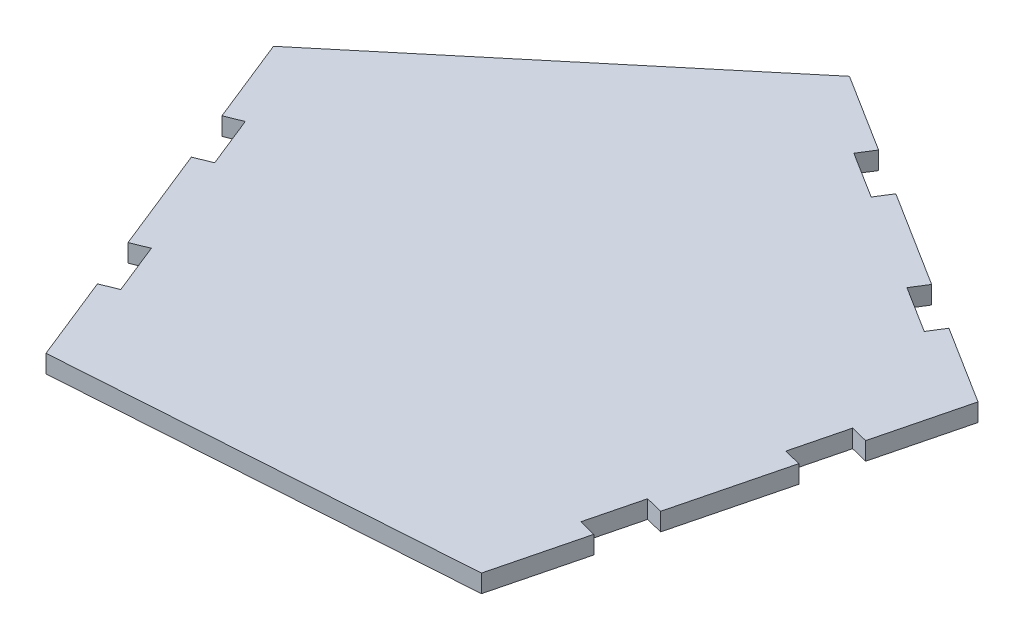
SolidWorks part; units mm, degrees
ref_plane "Front Plane" through (0, 0, 0) normal (0, 0, 1) x (1, 0, 0)
ref_plane "Top Plane" through (0, 0, 0) normal (0, 1, 0) x (1, 0, 0)
ref_plane "Right Plane" through (0, 0, 0) normal (1, 0, 0) x (0, 0, -1)
sketch "Sketch1" plane through (0, 0, 0) normal (0, 1, 0) x (1, 0, 0)
  line L1 (-59.9258, 15.1181) -> (-32.8962, -52.3211)
  line L2 (-32.8962, -52.3211) -> (39.5948, -47.4543)
  line L3 (39.5948, -47.4543) -> (57.3672, 22.9927)
  line L4 (57.3672, 22.9927) -> (-4.14, 61.6646)
  line L5 (-4.14, 61.6646) -> (-59.9258, 15.1181)
  circle A0 centre (0, 0) radius 50 construction
  dimension "D1" = 100
extrude "Boss-Extrude1" add sketch "Sketch1" along normal blind 3.18
sketch "Sketch2" plane through (0, 0, 0) normal (0, -1, 0) x (1, 0, 0)
  line L0 (-53.8107, 0.1392) -> (-50.859, -1.0438)
  line L1 (-53.8107, 0.1392) -> (-50.1723, 9.2172)
  line L2 (-50.859, -1.0438) -> (-47.2205, 8.0342)
  line L3 (-50.1723, 9.2172) -> (-47.2205, 8.0342)
  line L4 (-59.9258, -15.1181) -> (-32.8962, 52.3211) construction
  line L5 (-42.6498, 27.9858) -> (-39.0113, 37.0638)
  line L6 (-42.6498, 27.9858) -> (-39.6981, 26.8028)
  line L7 (-39.0113, 37.0638) -> (-36.0596, 35.8808)
  line L8 (-39.6981, 26.8028) -> (-36.0596, 35.8808)
  line L9 (-46.411, 18.6015) -> (-19.2439, 7.7129) construction
  line L10 (-40.8306, 32.5248) -> (-37.8788, 31.3418) construction
  dimension "D1" = 3.18
  dimension "D2" = 9.78
  dimension "D3" = 10.11
extrude "Female Cut" cut sketch "Sketch2" against normal through all
ref_axis "Axis1" through (0, 3.339, 0) along (0, -1, 0)
pattern_circular "CirPattern1" count 5 every 72 about axis through (0, 3.339, 0) along (0, -1, 0) skipping 1, 4 of "Female Cut"
sketch "Sketch3" [suppressed] plane through (0, 3.18, 0) normal (0, 1, 0) x (1, 0, 0)
  line L0 (0, 0) -> (-40.9819, 49.1167) construction
  line L1 (-49.5112, 27.9494) -> (-47.4739, 25.5077)
  line L2 (-49.5112, 27.9494) -> (-41.664, 34.4969)
  line L3 (-47.4739, 25.5077) -> (-39.6267, 32.0552)
  line L4 (-41.664, 34.4969) -> (-39.6267, 32.0552)
  line L5 (-4.4033, 65.5865) -> (-63.7371, 16.0796) construction
  line L6 (-74.0334, 7.4886) -> (-71.9961, 5.0469)
  line L7 (-74.0334, 7.4886) -> (2.7493, 71.5544)
  line L8 (-71.9961, 5.0469) -> (4.7866, 69.1127)
  line L9 (2.7493, 71.5544) -> (4.7866, 69.1127)
  line L14 (-26.4764, 47.1691) -> (-24.4391, 44.7274)
  line L15 (-26.4764, 47.1691) -> (-18.6292, 53.7166)
  line L16 (-24.4391, 44.7274) -> (-16.5919, 51.275)
  line L17 (-18.6292, 53.7166) -> (-16.5919, 51.275)
  line L18 (-45.5876, 31.2231) -> (-43.5503, 28.7815) construction
  line L20 (-9.7247, 57.0048) -> (-11.762, 59.4465) construction
  line M18 (-4.4033, 65.5865) -> (-63.7371, 16.0796)
  line M19 (-63.7371, 16.0796) -> (-34.9884, -55.6487)
  line M22 (61.0157, 24.4551) -> (-4.4033, 65.5865)
  dimension "D1" = 3.18
  dimension "D2" = 10.22
  dimension "D3" = 9.89
  dimension "D4" = 100
extrude "Male Cut" [suppressed] cut sketch "Sketch3" against normal blind 10 contours L8 L1 M19 M18 | L14 L7 L4 L8 | L17 L8 M18 M22
pattern_circular "CirPattern2" [suppressed] count 5 over 360 about axis through (0, 3.339, 0) along (0, -1, 0) of bodies 109
equation "\"kerf\"= .22mm"
equation "\"tabWidthF\"= 10 - \"kerf\""
equation "\"tabThickness\"= 3.18"
equation "\"D1@Sketch2\"=\"tabThickness\""
equation "\"tabWidthM\"= 10 + \"kerf\""
equation "\"halfkerf\"= \"kerf\" / 2.00mm"
equation "\"tabLength\" = \"kerf\" + 12"
